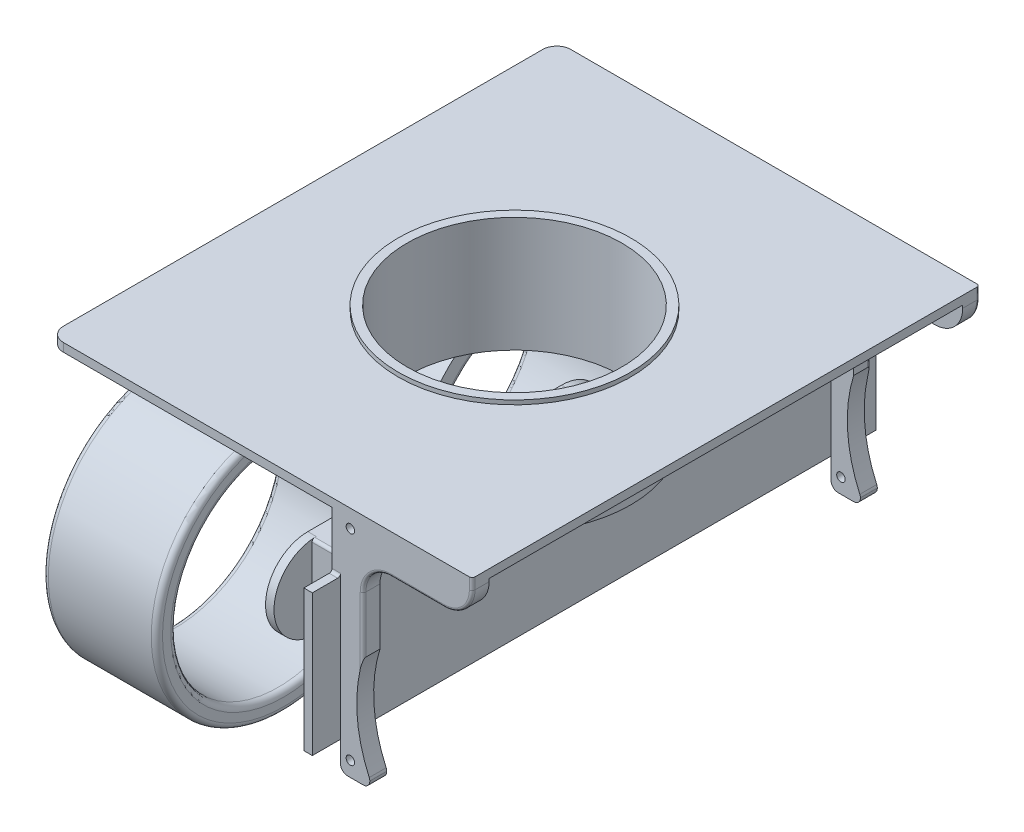
SolidWorks part; units mm, degrees
ref_plane "Plan de face" through (0, 0, 0) normal (0, 0, 1) x (1, 0, 0)
ref_plane "Plan de dessus" through (0, 0, 0) normal (0, 1, 0) x (1, 0, 0)
ref_plane "Plan de droite" through (0, 0, 0) normal (1, 0, 0) x (0, 0, -1)
sketch "Esquisse1" plane through (0, 0, 0) normal (0, 1, 0) x (1, 0, 0)
  line L0 (56, 129.6667) -> (206, -50.3333) construction
  line L1 (61, -50.3333) -> (206, -50.3333)
  line L2 (56, -45.3333) -> (56, 124.6667)
  line L3 (61, 129.6667) -> (206, 129.6667)
  line L4 (206, -50.3333) -> (206, 129.6667)
  line L5 (206, 129.6667) -> (56, -50.3333) construction
  line L6 (56, -20.4749) -> (56, -61.6958) construction
  line L7 (66.7691, -50.3333) -> (45.3389, -50.3333) construction
  arc A0 (61, -50.3333) -> (56, -45.3333) centre (61, -45.3333) cw
  arc A1 (56, 124.6667) -> (61, 129.6667) centre (61, 124.6667) cw
  circle A2 centre (131, 39.6667) radius 41.25
  point P8 (56, 129.6667)
  dimension "D3" = 5
  dimension "D4" = 82.5
  dimension "D1" = 180
  dimension "D2" = 150
extrude "Boss.-Extru.4" add sketch "Esquisse1" against normal blind 3 contours L4 L3 A1 L2 A0 L1 | A2
ref_plane "Plan1" through (0, 0, -129.6667) normal (0, 0, 1) x (1, 0, 0)
ref_plane "Plan2" through (0, 0, 50.3333) normal (0, 0, 1) x (1, 0, 0)
ref_plane "Plan3" through (0, 1.5, 0) normal (0, 1, 0) x (1, 0, 0)
sketch "Esquisse3" plane through (0, 1.5, 0) normal (0, 1, 0) x (1, 0, 0)
  circle A0 centre (131, 39.6667) radius 41.25
  circle A1 centre (131, 39.6667) radius 38.1
  dimension "D1" = 76.2
  dimension "D2" = 82.5
extrude "Boss.-Extru.5" add sketch "Esquisse3" against normal blind 40.78
sketch "Esquisse6" plane through (0, 0, -129.6667) normal (0, 0, 1) x (1, 0, 0)
  line L0 (206, -3) -> (159.3, -3)
  line L1 (89.75, -3) -> (172.25, -3) construction
  line L2 (159.3, -3) -> (159.3, -80.25)
  line L3 (161.8, -82.75) -> (169.7, -82.75)
  line L4 (206, -3) -> (206, -14) construction
  line L5 (206, -14) -> (159.3, -14) construction
  line L6 (167.3, -3) -> (167.3, -82.75) construction
  line L7 (196, -14) -> (177.3, -14)
  line L8 (167.3, -24) -> (167.3, -44)
  line L9 (169.7, -82.75) -> (169.7, -79.85) construction
  line L10 (169.7, -79.85) -> (159.3, -79.85) construction
  line L11 (206, -3) -> (206, -4)
  line L12 (169.7, -79.85) -> (169.7, -82.75)
  line L13 (162.8, -6.3) -> (162.8, -82.75) construction
  arc A0 (177.3, -14) -> (167.3, -24) centre (177.3, -24) ccw
  arc A1 (167.3, -44) -> (169.7, -79.85) centre (215.0568, -58.8082) ccw
  arc A3 (196, -14) -> (206, -4) centre (196, -4) ccw
  arc A4 (159.3, -80.25) -> (161.8, -82.75) centre (161.8, -80.25) ccw
  circle A5 centre (162.8, -6.3) radius 1.5
  circle A6 centre (162.8, -77.45) radius 1.5
  point P15 (167.3, -14)
  point P27 (159.3, -82.75)
  dimension "D6" = 10
  dimension "D9" = 10
  dimension "D10" = 2.5
  dimension "D11" = 3.3
  dimension "D13" = 5.3
  dimension "D1" = 46.7
  dimension "D2" = 79.75
  dimension "D3" = 10.4
  dimension "D4" = 11
  dimension "D5" = 8
  dimension "D7" = 20
  dimension "D8" = 2.9
  dimension "D12" = 3.5
extrude "Boss.-Extru.8" add sketch "Esquisse6" along normal blind 6 contours A3 L11 L0 L2 A4 L3 L12 A1 L8 A0 L7
fillet "Congé14" radius 2.35 1 edges at (169.7, -79.85, -126.6667)
fillet "Congé15" radius 2.35 1 edges at (169.7, -82.75, -126.6667)
sketch "Esquisse8" plane through (0, 0, 50.3333) normal (0, 0, 1) x (1, 0, 0)
  line L0 (206, -3) -> (159.3, -3)
  line L1 (159.3, -3) -> (159.3, -80.25)
  line L2 (161.8, -82.75) -> (169.7, -82.75)
  line L3 (206, -3) -> (206, -14) construction
  line L4 (206, -14) -> (159.3, -14) construction
  line L5 (167.3, -3) -> (167.3, -82.75) construction
  line L6 (196, -14) -> (177.3, -14)
  line L7 (167.3, -24) -> (167.3, -44)
  line L8 (169.7, -82.75) -> (169.7, -79.85) construction
  line L9 (169.7, -79.85) -> (159.3, -79.85) construction
  line L10 (206, -3) -> (206, -4)
  line L11 (169.7, -79.85) -> (169.7, -82.75)
  line L12 (61, -3) -> (206, -3) construction
  line L13 (162.8, -6.3) -> (162.8, -82.75) construction
  arc A0 (177.3, -14) -> (167.3, -24) centre (177.3, -24) ccw
  arc A1 (167.3, -44) -> (169.7, -79.85) centre (215.0568, -58.8082) ccw
  arc A2 (196, -14) -> (206, -4) centre (196, -4) ccw
  arc A3 (159.3, -80.25) -> (161.8, -82.75) centre (161.8, -80.25) ccw
  circle A4 centre (162.8, -6.3) radius 1.5
  circle A5 centre (162.8, -77.45) radius 1.5
  dimension "D4" = 10
  dimension "D7" = 10
  dimension "D8" = 2.5
  dimension "D10" = 3.5
  dimension "D12" = 5.3
  dimension "D1" = 46.7
  dimension "D2" = 11
  dimension "D3" = 8
  dimension "D5" = 20
  dimension "D6" = 2.9
  dimension "D9" = 77.25
  dimension "D11" = 3.3
extrude "Boss.-Extru.9" add sketch "Esquisse8" against normal blind 6
fillet "Congé16" radius 2.35 1 edges at (169.7, -82.75, 47.3333)
fillet "Congé17" radius 2.35 1 edges at (169.7, -79.85, 47.3333)
sketch "Esquisse11" plane through (0, 0, -129.6667) normal (0, 0, -1) x (-1, 0, 0)
  line L0 (-159.3, -3) -> (-159.3, -80.25) construction
  line L2 (-61, -3) -> (-159.3, -3) construction
  circle A0 centre (-162.8, -6.3) radius 1.5
  dimension "D1" = 3.5
  dimension "D2" = 3.3
extrude "Enlèv. mat.-Extru.2" cut sketch "Esquisse11" against normal blind 10
sketch "Esquisse12" plane through (0, 0, -129.6667) normal (0, 0, -1) x (-1, 0, 0)
  line L0 (-162.8, -6.3) -> (-162.8, -82.75) construction
  line L1 (-161.8, -82.75) -> (-167.35, -82.75) construction
  circle A0 centre (-162.8, -77.45) radius 1.5
  dimension "D1" = 5.3
extrude "Enlèv. mat.-Extru.3" cut sketch "Esquisse12" against normal blind 10
fillet "Congé18" radius 1 5 edges at (167.3, -34, 50.3333) (170.2289, -16.9289, 50.3333) (186.65, -14, 50.3333) (203.0711, -11.0711, 50.3333) (206, -2, 50.3333)
fillet "Congé19" radius 1 5 edges at (206, -2, -129.6667) (203.0711, -11.0711, -129.6667) (167.3, -34, -129.6667) (170.2289, -16.9289, -129.6667) (186.65, -14, -129.6667)
ref_plane "Plan5" through (159.3, 0, 0) normal (-1, 0, 0) x (0, 0, 1)
sketch "Esquisse13" plane through (159.3, 0, 0) normal (-1, 0, 0) x (0, 0, 1)
  line L0 (-129.6667, -3) -> (-129.6667, -21.75)
  line L1 (-129.6667, -3) -> (-129.6667, -80.25) construction
  line L2 (-130.6667, -22.75) -> (-139.6667, -22.75)
  line L3 (-139.6667, -22.75) -> (-139.6667, -72.75)
  line L4 (-139.6667, -72.75) -> (50.3333, -72.75)
  line L5 (50.3333, -3) -> (50.3333, -80.25) construction
  line L6 (50.3333, -72.75) -> (60.3333, -72.75)
  line L7 (60.3333, -72.75) -> (60.3333, -22.75)
  line L8 (60.3333, -22.75) -> (51.3333, -22.75)
  line L9 (50.3333, -21.75) -> (50.3333, -3)
  line L11 (50.3333, -3) -> (1.5833, -3)
  line L12 (1.5833, -3) -> (1.5833, -38.5)
  line L13 (-129.6667, -3) -> (-80.9167, -3)
  line L14 (-80.9167, -3) -> (-80.9167, -38.5)
  line L15 (-78.4167, -41) -> (-0.9167, -41)
  arc A0 (51.3333, -22.75) -> (50.3333, -21.75) centre (51.3333, -21.75) cw
  arc A1 (-129.6667, -21.75) -> (-130.6667, -22.75) centre (-130.6667, -21.75) cw
  arc A2 (-80.9167, -38.5) -> (-78.4167, -41) centre (-78.4167, -38.5) ccw
  arc A3 (1.5833, -38.5) -> (-0.9167, -41) centre (-0.9167, -38.5) cw
  point P26 (50.3333, -22.75)
  point P29 (-129.6667, -22.75)
  point P34 (1.5833, -41)
  dimension "D4" = 1
  dimension "D5" = 1
  dimension "D7" = 2.5
  dimension "D1" = 19.75
  dimension "D2" = 10
  dimension "D3" = 10
  dimension "D6" = 38
extrude "Boss.-Extru.10" add sketch "Esquisse13" along normal blind 3
ref_plane "Plan6" through (0, 0, 6.8333) normal (0, 0, 1) x (1, 0, 0)
sketch "Esquisse14" plane through (0, 0, 6.8333) normal (0, 0, 1) x (1, 0, 0)
  line L0 (156.3, -3) -> (156.3, -62.75)
  line L1 (156.3, -72.75) -> (156.3, -22.75) construction
  line L2 (156.3, -3) -> (84.4, -3)
  line L3 (61, -3) -> (156.3, -3) construction
  line L4 (84.4, -3) -> (84.4, -19.75)
  line L5 (126.3, -3) -> (126.3, -94.8206) construction
  line L6 (156.3, -62.75) -> (153.3, -62.75)
  line L8 (84.4, -19.75) -> (81.5122, -19.75)
  line L9 (78.1823, -21.0202) -> (72.8562, -25.7752)
  line L10 (71.1861, -29.75) -> (94.1861, -29.75)
  line L11 (94.1861, -29.75) -> (94.1861, -32.75)
  line L12 (94.1861, -32.75) -> (156.3, -32.75) construction
  line L13 (71.1861, -29.505) -> (71.1861, -29.75)
  line L14 (126.3, -94.8206) -> (126.3, -37.75)
  line L15 (121.3, -32.75) -> (94.1861, -32.75)
  line L16 (153.3, -62.75) -> (153.3, -72.75)
  line L18 (126.3, -94.8206) -> (129.3702, -94.8206)
  line L19 (129.3702, -94.8206) -> (153.3, -72.75)
  arc A0 (126.3, -37.75) -> (121.3, -32.75) centre (121.3, -37.75) ccw
  arc A1 (72.8562, -25.7752) -> (71.1861, -29.505) centre (76.1861, -29.505) ccw
  arc A2 (81.5122, -19.75) -> (78.1823, -21.0202) centre (81.5122, -24.75) ccw
  point P21 (126.3, -32.75)
  dimension "D8" = 5
  dimension "D9" = 5
  dimension "D10" = 5
  dimension "D1" = 59.75
  dimension "D2" = 71.9
  dimension "D3" = 16.75
  dimension "D4" = 30
  dimension "D5" = 29.75
  dimension "D6" = 10
  dimension "D7" = 23
extrude "Boss.-Extru.11" add sketch "Esquisse14" against normal blind 3 contours L14 A0 L15 L11 L10 L13 A1 L9 A2 L8 L4 L2 L0 L6 L16 L19 L18
fillet "Congé20" radius 5 1 edges at (129.3702, -94.8206, 5.3333)
ref_plane "Plan7" through (0, 0, -86.1667) normal (0, 0, -1) x (-1, 0, 0)
sketch "Esquisse15" plane through (0, 0, -86.1667) normal (0, 0, -1) x (-1, 0, 0)
  line L3 (-61, -3) -> (-156.3, -3) construction
  line L9 (-156.3, -3) -> (-156.3, -21.75) construction
  line L16 (-84.4, -3) -> (-84.4, -19.75) construction
  line L17 (-94.1861, -32.75) -> (-156.3, -32.75) construction
  line L18 (-126.3, -3) -> (-126.3, -94.8206) construction
  line L19 (-129.3702, -94.8206) -> (-153.3, -72.75)
  line L20 (-126.3, -94.8206) -> (-129.3702, -94.8206)
  line L21 (-153.3, -62.75) -> (-153.3, -72.75)
  line L22 (-121.3, -32.75) -> (-94.1861, -32.75)
  line L23 (-126.3, -94.8206) -> (-126.3, -37.75)
  line L24 (-71.1861, -29.505) -> (-71.1861, -29.75)
  line L25 (-94.1861, -29.75) -> (-94.1861, -32.75)
  line L26 (-71.1861, -29.75) -> (-94.1861, -29.75)
  line L27 (-78.1823, -21.0202) -> (-72.8562, -25.7752)
  line L28 (-84.4, -19.75) -> (-81.5122, -19.75)
  line L29 (-156.3, -62.75) -> (-153.3, -62.75)
  line L30 (-84.4, -3) -> (-84.4, -19.75)
  line L31 (-156.3, -3) -> (-84.4, -3)
  line L32 (-156.3, -3) -> (-156.3, -62.75)
  arc A3 (-81.5122, -19.75) -> (-78.1823, -21.0202) centre (-81.5122, -24.75) cw
  arc A4 (-72.8562, -25.7752) -> (-71.1861, -29.505) centre (-76.1861, -29.505) cw
  arc A5 (-126.3, -37.75) -> (-121.3, -32.75) centre (-121.3, -37.75) cw
extrude "Boss.-Extru.12" add sketch "Esquisse15" against normal blind 3
fillet "Congé21" radius 5 1 edges at (129.3702, -94.8206, -84.6667)
ref_plane "Plan8" through (156.3, -72.75, -139.6667) normal (0, 0, 1) x (1, 0, 0)
sketch "Esquisse16" plane through (0, 0, 6.8333) normal (0, 0, 1) x (1, 0, 0)
  line L0 (156.3, -3) -> (84.4, -3) construction
  line L1 (94.4, -8) -> (121.4, -8)
  line L2 (89.4, -13) -> (89.4, -20)
  line L3 (94.4, -25) -> (121.4, -25)
  line L4 (126.4, -13) -> (126.4, -20)
  line L5 (84.4, -3) -> (84.4, -19.75) construction
  line L6 (132.3, -70) -> (146.3475, -70)
  line L7 (136.4, -8) -> (146.4, -8)
  line L8 (131.4, -13) -> (131.4, -46)
  line L9 (136.4, -51) -> (146.4, -51)
  line L10 (151.4, -13) -> (151.4, -46)
  line L11 (147.0255, -71.7351) -> (132.978, -84.6912)
  line L12 (131.3, -83.9561) -> (131.3, -71)
  line L14 (126.3, -94.8206) -> (126.3, -37.75) construction
  line L16 (130.8064, -93.496) -> (153.3, -72.75) construction
  arc A0 (89.4, -20) -> (94.4, -25) centre (94.4, -20) ccw
  arc A1 (94.4, -8) -> (89.4, -13) centre (94.4, -13) ccw
  arc A2 (121.4, -8) -> (126.4, -13) centre (121.4, -13) cw
  arc A3 (121.4, -25) -> (126.4, -20) centre (121.4, -20) ccw
  arc A4 (131.4, -46) -> (136.4, -51) centre (136.4, -46) ccw
  arc A5 (146.4, -51) -> (151.4, -46) centre (146.4, -46) ccw
  arc A6 (146.4, -8) -> (151.4, -13) centre (146.4, -13) cw
  arc A7 (136.4, -8) -> (131.4, -13) centre (136.4, -13) ccw
  arc A8 (131.3, -71) -> (132.3, -70) centre (132.3, -71) cw
  arc A9 (131.3, -83.9561) -> (132.978, -84.6912) centre (132.3, -83.9561) ccw
  arc A10 (146.3475, -70) -> (147.0255, -71.7351) centre (146.3475, -71) cw
  dimension "D5" = 5
  dimension "D10" = 5
  dimension "D14" = 1
  dimension "D1" = 5
  dimension "D2" = 5
  dimension "D3" = 17
  dimension "D4" = 37
  dimension "D6" = 5
  dimension "D7" = 5
  dimension "D8" = 20
  dimension "D9" = 43
  dimension "D11" = 5
  dimension "D12" = 5
  dimension "D13" = 19
extrude "Enlèv. mat.-Extru.5" cut sketch "Esquisse16" against normal blind 3 contours L3 A3 L4 A2 L1 A1 L2 A0 | L8 A4 L9 A5 L10 A6 L7 A7 | L6 A10 L11 A9 L12 A8
sketch "Esquisse18" plane through (0, 0, -86.1667) normal (0, 0, -1) x (-1, 0, 0)
  line L0 (-121.4, -8) -> (-94.4, -8)
  line L1 (-126.4, -13) -> (-126.4, -20)
  line L2 (-121.4, -25) -> (-94.4, -25)
  line L3 (-89.4, -13) -> (-89.4, -20)
  line L4 (-84.4, -19.75) -> (-84.4, -3) construction
  line L5 (-84.4, -3) -> (-156.3, -3) construction
  line L6 (-146.4, -8) -> (-136.4, -8)
  line L7 (-151.4, -13) -> (-151.4, -46)
  line L8 (-146.4, -51) -> (-136.4, -51)
  line L9 (-131.4, -13) -> (-131.4, -46)
  line L10 (-146.3475, -70) -> (-132.3, -70)
  line L11 (-131.3, -71) -> (-131.3, -83.9561)
  line L12 (-132.978, -84.6912) -> (-147.0255, -71.7351)
  line L14 (-153.3, -72.75) -> (-130.8064, -93.496) construction
  line L15 (-126.3, -94.8206) -> (-126.3, -37.75) construction
  arc A0 (-126.4, -20) -> (-121.4, -25) centre (-121.4, -20) ccw
  arc A1 (-121.4, -8) -> (-126.4, -13) centre (-121.4, -13) ccw
  arc A2 (-94.4, -8) -> (-89.4, -13) centre (-94.4, -13) cw
  arc A3 (-94.4, -25) -> (-89.4, -20) centre (-94.4, -20) ccw
  arc A4 (-151.4, -46) -> (-146.4, -51) centre (-146.4, -46) ccw
  arc A5 (-136.4, -51) -> (-131.4, -46) centre (-136.4, -46) ccw
  arc A6 (-136.4, -8) -> (-131.4, -13) centre (-136.4, -13) cw
  arc A7 (-146.4, -8) -> (-151.4, -13) centre (-146.4, -13) ccw
  arc A8 (-131.3, -83.9561) -> (-132.978, -84.6912) centre (-132.3, -83.9561) cw
  arc A9 (-132.3, -70) -> (-131.3, -71) centre (-132.3, -71) cw
  arc A10 (-146.3475, -70) -> (-147.0255, -71.7351) centre (-146.3475, -71) ccw
  dimension "D7" = 5
  dimension "D13" = 1
  dimension "D1" = 17
  dimension "D2" = 37
  dimension "D3" = 5
  dimension "D4" = 5
  dimension "D5" = 20
  dimension "D6" = 43
  dimension "D8" = 5
  dimension "D9" = 5
  dimension "D10" = 5
  dimension "D11" = 5
  dimension "D12" = 19
extrude "Enlèv. mat.-Extru.6" cut sketch "Esquisse18" against normal blind 3 contours L2 A3 L3 A2 L0 A1 L1 A0 | L10 A10 L12 A8 L11 A9 | L9 A5 L8 A4 L7 A7 L6 A6 region at (107.9, -16.5, -86.1667) region at (137.1186, -75.3901, -86.1667)
ref_plane "Plan11" through (0, -62.75, 0) normal (0, -1, 0) x (-1, 0, 0)
sketch "Esquisse20" plane through (0, -62.75, 0) normal (0, -1, 0) x (-1, 0, 0)
  line L0 (-121.3, -3.8333) -> (-94.1861, -3.8333) construction
  line L1 (-156.3, 83.1667) -> (-105.7, 83.1667)
  line L2 (-156.3, 83.1667) -> (-156.3, -3.8333)
  line L3 (-156.3, -3.8333) -> (-105.7, -3.8333)
  line L4 (-105.7, 83.1667) -> (-105.7, -3.8333)
  line L5 (-156.3, 83.1667) -> (-105.7, -3.8333) construction
  line L6 (-105.7, 83.1667) -> (-156.3, -3.8333) construction
  line L8 (-115.7, 78.1667) -> (-146.3, 78.1667)
  line L9 (-110.7, 73.1667) -> (-110.7, 63.1667)
  line L10 (-115.7, 58.1667) -> (-146.3, 58.1667)
  line L11 (-151.3, 73.1667) -> (-151.3, 63.1667)
  line L12 (-115.7, 21.1667) -> (-146.3, 21.1667)
  line L13 (-110.7, 16.1667) -> (-110.7, 6.1667)
  line L14 (-115.7, 1.1667) -> (-146.3, 1.1667)
  line L15 (-151.3, 16.1667) -> (-151.3, 6.1667)
  line L16 (-138, 46.6667) -> (-124, 46.6667) construction
  line L17 (-138, 46.6667) -> (-138, 32.6667) construction
  line L18 (-138, 32.6667) -> (-124, 32.6667) construction
  line L19 (-124, 46.6667) -> (-124, 32.6667) construction
  line L20 (-138, 46.6667) -> (-124, 32.6667) construction
  line L21 (-138, 32.6667) -> (-124, 46.6667) construction
  arc A0 (-115.7, 21.1667) -> (-110.7, 16.1667) centre (-115.7, 16.1667) cw
  arc A1 (-110.7, 6.1667) -> (-115.7, 1.1667) centre (-115.7, 6.1667) cw
  arc A2 (-146.3, 1.1667) -> (-151.3, 6.1667) centre (-146.3, 6.1667) cw
  arc A3 (-146.3, 21.1667) -> (-151.3, 16.1667) centre (-146.3, 16.1667) ccw
  arc A4 (-146.3, 78.1667) -> (-151.3, 73.1667) centre (-146.3, 73.1667) ccw
  arc A5 (-146.3, 58.1667) -> (-151.3, 63.1667) centre (-146.3, 63.1667) cw
  arc A6 (-110.7, 63.1667) -> (-115.7, 58.1667) centre (-115.7, 63.1667) cw
  arc A7 (-115.7, 78.1667) -> (-110.7, 73.1667) centre (-115.7, 73.1667) cw
  circle A8 centre (-131, 39.6667) radius 2.5
  circle A9 centre (-124, 46.6667) radius 1
  circle A10 centre (-124, 32.6667) radius 1
  circle A11 centre (-138, 32.6667) radius 1
  circle A12 centre (-138, 46.6667) radius 1
  point P7 (-131, 39.6667)
  point P8 (-131, 39.6667)
  dimension "D9" = 5
  dimension "D1" = 5
  dimension "D2" = 5
  dimension "D3" = 5
  dimension "D4" = 5
  dimension "D5" = 20
  dimension "D6" = 20
  dimension "D7" = 5
  dimension "D8" = 5
extrude "Boss.-Extru.13" add sketch "Esquisse20" against normal blind 3
sketch "Esquisse21" plane through (0, 0, -86.1667) normal (0, 0, -1) x (-1, 0, 0)
  line L0 (-105.7, -59.75) -> (-105.7, -62.75) construction
  line L1 (-126.3, -59.75) -> (-105.7, -59.75)
  line L2 (-126.3, -59.75) -> (-126.3, -94.8206)
  line L3 (-126.3, -94.8206) -> (-105.7, -94.8206)
  line L4 (-105.7, -59.75) -> (-105.7, -94.8206)
  dimension "D1" = 0
extrude "Boss.-Extru.14" add sketch "Esquisse21" against normal blind 3
sketch "Esquisse22" plane through (0, 0, 6.8333) normal (0, 0, 1) x (1, 0, 0)
  line L1 (126.3, -59.75) -> (105.7, -59.75)
  line L2 (126.3, -59.75) -> (126.3, -94.8206)
  line L3 (126.3, -94.8206) -> (105.7, -94.8206)
  line L4 (105.7, -59.75) -> (105.7, -94.8206)
extrude "Boss.-Extru.15" add sketch "Esquisse22" against normal blind 3 contours L2 L3 L4 L1
fillet "Congé22" radius 1 1 edges at (116, -59.75, 6.8333)
fillet "Congé23" radius 1 1 edges at (116, -59.75, -86.1667)
ref_plane "Plan12" through (105.7, 0, 0) normal (-1, 0, 0) x (0, 0, 1)
sketch "Esquisse23" plane through (105.7, 0, 0) normal (-1, 0, 0) x (0, 0, 1)
  line L0 (5.8333, -59.75) -> (-85.1667, -59.75) construction
  line L1 (-84.6667, -89.75) -> (5.3333, -89.75)
  line L2 (-84.6667, -89.75) -> (-84.6667, -59.75) construction
  line L3 (-84.6667, -59.75) -> (5.3333, -59.75)
  line L4 (5.3333, -89.75) -> (5.3333, -59.75) construction
  line L5 (-86.1667, -94.8206) -> (-86.1667, -60.75) construction
  line L6 (6.8333, -60.75) -> (6.8333, -94.8206) construction
  line L7 (-39.6667, -59.75) -> (-39.6667, -89.75) construction
  line L9 (-34.6667, -67.75) -> (-9.6667, -67.75)
  line L10 (-34.6667, -67.75) -> (-34.6667, -85.75)
  line L11 (-34.6667, -85.75) -> (-9.6667, -85.75)
  line L12 (-9.6667, -67.75) -> (-9.6667, -85.75)
  line L13 (-69.6667, -67.75) -> (-44.6667, -67.75)
  line L14 (-69.6667, -67.75) -> (-69.6667, -85.75)
  line L15 (-69.6667, -85.75) -> (-44.6667, -85.75)
  line L16 (-44.6667, -67.75) -> (-44.6667, -85.75)
  arc A0 (5.3333, -59.75) -> (5.3333, -89.75) centre (5.3333, -74.75) cw
  arc A1 (-84.6667, -59.75) -> (-84.6667, -89.75) centre (-84.6667, -74.75) ccw
  dimension "D1" = 90
  dimension "D2" = 30
  dimension "D3" = 1.5
  dimension "D4" = 1.5
  dimension "D5" = 5
  dimension "D6" = 5
  dimension "D7" = 25
  dimension "D8" = 25
  dimension "D9" = 18
  dimension "D10" = 18
  dimension "D11" = 8
  dimension "D12" = 8
sketch "Esquisse24" plane through (0, 0, 6.8333) normal (0, 0, 1) x (1, 0, 0)
  line L0 (105.7, -89.75) -> (134.868, -89.75) construction
  line L1 (105.7, -89.75) -> (105.7, -59.75) construction
  line L2 (105.7, -89.75) -> (105.7, -59.75) construction
  line L3 (130.8064, -93.496) -> (153.3, -72.75) construction
  line L4 (105.7, -89.75) -> (134.868, -89.75)
  line L5 (134.868, -89.75) -> (134.868, -94.8206)
  line L6 (134.868, -94.8206) -> (105.7, -94.8206)
  line L7 (105.7, -94.8206) -> (105.7, -89.75)
extrude "Enlèv. mat.-Extru.7" cut sketch "Esquisse24" against normal blind 93 contours L6 L7 L4 L5
fillet "Congé24" radius 5 1 edges at (134.868, -89.75, -84.6667)
fillet "Congé25" radius 5 1 edges at (134.868, -89.75, 5.3333)
fillet "Congé26" radius 5 1 edges at (153.3, -72.75, -84.6667)
fillet "Congé27" radius 5 1 edges at (153.3, -72.75, 5.3333)
extrude "Boss.-Extru.17" add sketch "Esquisse23" along normal blind 3 contours L3 A1 L1 A0 L13 L16 L15 L14 L9 L12 L11 L10 region at (105.7, -74.032, -39.6667)
ref_plane "Plan13" through (94.1861, 0, 0) normal (-1, 0, 0) x (0, 0, 1)
sketch "Esquisse25" plane through (102.7, 0, 0) normal (-1, 0, 0) x (0, 0, 1)
  line L1 (-93.0507, -82.4499) -> (-76.2826, -82.4499)
  line L2 (-93.0507, -82.4499) -> (-93.0507, -67.0501)
  line L3 (-93.0507, -67.0501) -> (-76.2826, -67.0501)
  line L4 (-76.2826, -82.4499) -> (-76.2826, -67.0501)
  line L5 (-93.0507, -82.4499) -> (-76.2826, -67.0501) construction
  line L6 (-93.0507, -67.0501) -> (-76.2826, -82.4499) construction
  line L7 (-3.8666, -84.1049) -> (14.5332, -84.1049)
  line L8 (-3.8666, -84.1049) -> (-3.8666, -65.3951)
  line L9 (-3.8666, -65.3951) -> (14.5332, -65.3951)
  line L10 (14.5332, -84.1049) -> (14.5332, -65.3951)
  line L11 (-3.8666, -84.1049) -> (14.5332, -65.3951) construction
  line L12 (-3.8666, -65.3951) -> (14.5332, -84.1049) construction
  circle A0 centre (-84.6667, -74.75) radius 15 construction
  arc A1 (-84.6667, -59.75) -> (-84.6667, -89.75) centre (-84.6667, -74.75) ccw construction
  circle A2 centre (5.3333, -74.75) radius 15 construction
  arc A3 (5.3333, -89.75) -> (5.3333, -59.75) centre (5.3333, -74.75) ccw construction
sketch "Esquisse26" plane through (94.1861, 0, 0) normal (-1, 0, 0) x (0, 0, 1)
  line L0 (-39.9667, -69.35) -> (-39.3667, -69.35) construction
  line L3 (-39.3667, -80.15) -> (-39.9667, -80.15) construction
  line L4 (-39.9667, -80.15) -> (-39.3667, -80.15)
  line L5 (-39.9667, -69.35) -> (-39.3667, -69.35)
  circle A0 centre (-84.6667, -74.75) radius 45.025 construction
  circle A1 centre (5.3333, -74.75) radius 45.025 construction
  circle A4 centre (5.3333, -74.75) radius 38.1
  circle A5 centre (-84.6667, -74.75) radius 38.1
  arc A6 (-39.9667, -69.35) -> (-39.9667, -80.15) centre (-84.6667, -74.75) ccw
  arc A7 (-39.3667, -80.15) -> (-39.3667, -69.35) centre (5.3333, -74.75) ccw
  dimension "D1" = 76.2
  dimension "D2" = 76.2
  dimension "D3" = 0.6
  dimension "D4" = 0.6
extrude "Boss.-Extru.21" add sketch "Esquisse26" along normal blind 40.5
fillet "Congé33" radius 2 1 edges at (53.6861, -74.75, -129.6917)
fillet "Congé34" radius 2 1 edges at (53.6861, -74.75, -46.5667)
fillet "Congé35" radius 2 1 edges at (53.6861, -74.75, 43.4333)
fillet "Congé36" radius 2 1 edges at (53.6861, -74.75, 50.3583)
fillet "Congé37" radius 2 1 edges at (53.6861, -80.15, -39.6667)
fillet "Congé38" radius 2 1 edges at (53.6861, -69.35, -39.6667)
fillet "Congé39" radius 2 1 edges at (94.1861, -105.1745, -117.857)
fillet "Congé40" radius 2 1 edges at (94.1861, -74.75, -46.5667)
fillet "Congé41" radius 2 1 edges at (94.1861, -105.1745, 38.5237)
fillet "Congé42" radius 2 1 edges at (94.1861, -74.75, 43.4333)
